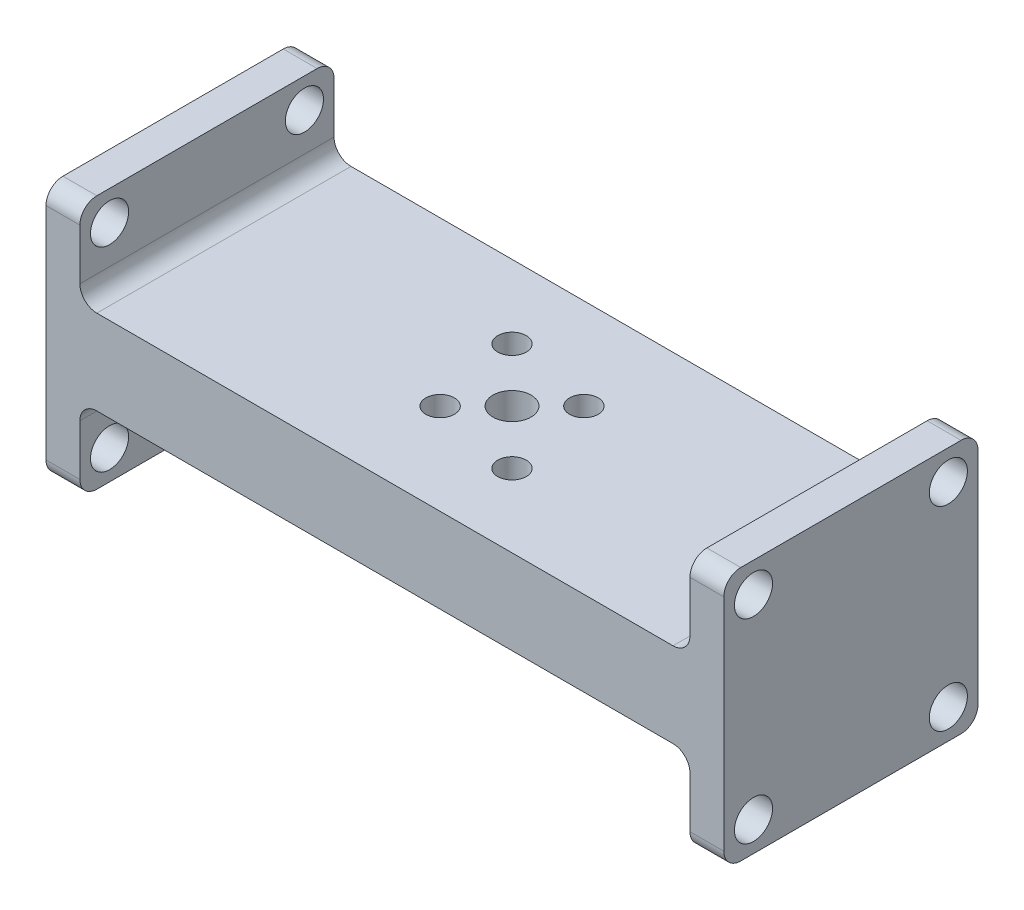
SolidWorks part; units mm, degrees
ref_plane "Front Plane" through (0, 0, 0) normal (0, 0, 1) x (1, 0, 0)
ref_plane "Top Plane" through (0, 0, 0) normal (0, 1, 0) x (1, 0, 0)
ref_plane "Right Plane" through (0, 0, 0) normal (1, 0, 0) x (0, 0, -1)
sketch "Sketch2" plane through (0, 0, 0) normal (0, 1, 0) x (1, 0, 0)
  line L0 (-4.2426, -4.2426) -> (4.2426, 4.2426) construction
  line L1 (-36, 15) -> (36, 15)
  line L2 (-36, 15) -> (-36, -15)
  line L3 (-36, -15) -> (36, -15)
  line L4 (36, 15) -> (36, -15)
  line L5 (6.364, -6.364) -> (-6.364, 6.364) construction
  circle A0 centre (0, 0) radius 2.25
  circle A1 centre (-6.364, 6.364) radius 1.6875
  circle A2 centre (6.364, -6.364) radius 1.6875
  circle A3 centre (4.2426, 4.2426) radius 1.6875
  circle A4 centre (-4.2426, -4.2426) radius 1.6875
  point P4 (0, 15)
  point P6 (-36, 0)
  point P12 (0, 0)
  point P15 (0, 0)
  dimension "D3" = 4.5
  dimension "D8" = 3.375
  dimension "D1" = 72
  dimension "D2" = 30
  dimension "D4" = 90
  dimension "D5" = 45
  dimension "D6" = 18
  dimension "D7" = 12
extrude "Boss-Extrude1" add sketch "Sketch2" along normal blind 10 contours A0 | A1 | L2 L3 L4 L1 | A4 | A3 | A2 region at (0, 0, 0) region at (-6.364, 0, -6.364)
sketch "Sketch3" plane through (-36, 0, 0) normal (-1, 0, 0) x (0, 0, 1)
  line L0 (-15, 10) -> (-15, 0) construction
  line L1 (-15, 20) -> (15, 20)
  line L2 (-15, 20) -> (-15, -10)
  line L3 (-15, -10) -> (15, -10)
  line L4 (15, 20) -> (15, -10)
  line L5 (15, 10) -> (15, 0) construction
  line L6 (-15, 10) -> (-15, 0) construction
  line L7 (0, 20) -> (0, -10) construction
  line L8 (-15, 5) -> (15, 5) construction
  circle A0 centre (-11.5, 16.5) radius 2.25
  circle A1 centre (-11.5, -6.5) radius 2.25
  circle A2 centre (11.5, -6.5) radius 2.25
  circle A3 centre (11.5, 16.5) radius 2.25
  point P8 (-15, 5)
  point P9 (-15, 5)
  dimension "D4" = 4.5
  dimension "D1" = 30
  dimension "D2" = 3.5
  dimension "D3" = 3.5
extrude "Boss-Extrude2" add sketch "Sketch3" along normal blind 4 contours A0 | A3 | A1 | A2 | L2 L3 L4 L1 region at (-36, 16.5, -11.5) region at (-36, -6.5, -11.5) region at (-36, -6.5, 11.5) region at (-36, 16.5, 11.5)
mirror "Mirror1" about plane through (0, 0, 0) normal (1, 0, 0) of "Boss-Extrude2"
fillet "Fillet1" radius 2 4 edges at (-36, 0, 0) (36, 0, 0) (36, 10, 0) (-36, 10, 0)
fillet "Fillet2" radius 2 8 edges at (38, -10, -15) (-38, -10, -15) (38, -10, 15) (38, 20, 15) (38, 20, -15) (-38, -10, 15) (-38, 20, 15) (-38, 20, -15)
